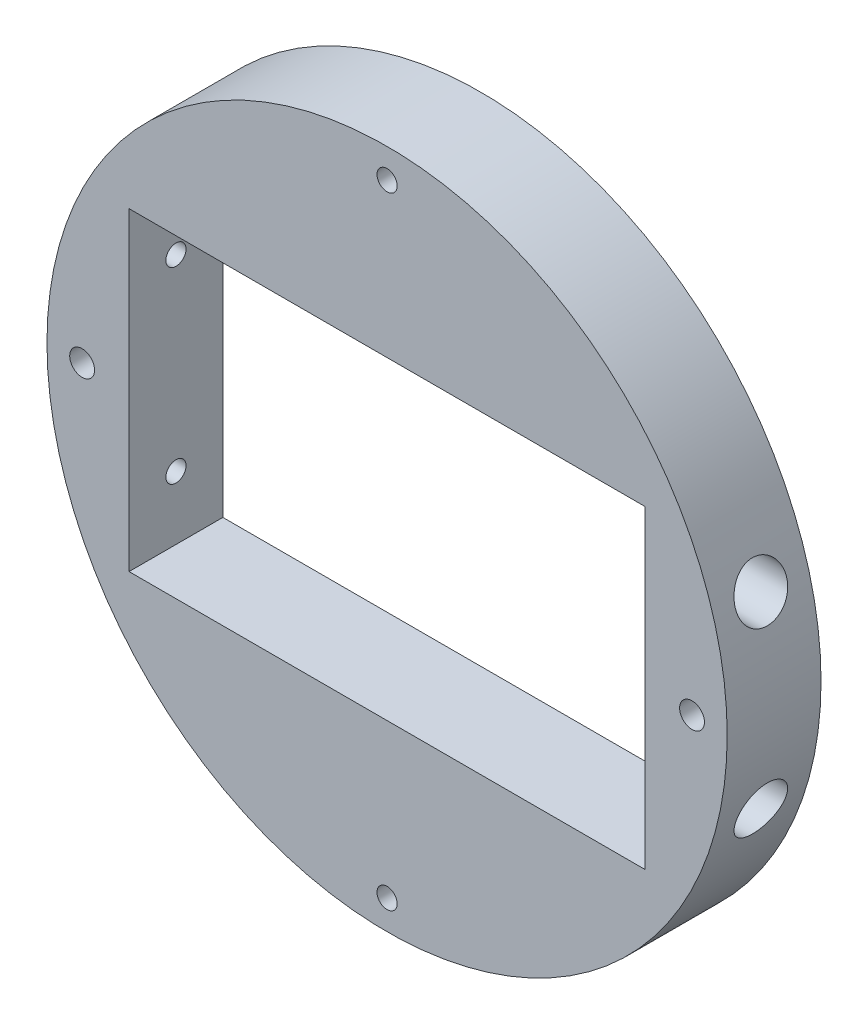
SolidWorks part; units mm, degrees
ref_plane "前视基准面" through (0, 0, 0) normal (0, 0, 1) x (1, 0, 0)
ref_plane "上视基准面" through (0, 0, 0) normal (0, 1, 0) x (1, 0, 0)
ref_plane "右视基准面" through (0, 0, 0) normal (1, 0, 0) x (0, 0, -1)
other "Configuration Table"
sketch "草图3" plane through (0, 0, 0) normal (0, 0, 1) x (1, 0, 0)
  line L1 (0, 72.5) -> (0, 60)
  line L2 (20, 60) -> (-20, 60) construction
  line L3 (0, -60) -> (0, -72.5)
  line L4 (-20, -60) -> (20, -60) construction
  line L5 (47, 33.5) -> (63, 33.5) construction
  line L6 (-55, -33.5) -> (55, -33.5)
  line L7 (-55, -33.5) -> (-55, 33.5)
  line L8 (-55, 33.5) -> (55, 33.5)
  line L9 (55, -33.5) -> (55, 33.5)
  line L10 (-55, -33.5) -> (55, 33.5) construction
  line L11 (-55, 33.5) -> (55, -33.5) construction
  circle A0 centre (0, 0) radius 72.5
  circle A1 centre (0, 66.25) radius 2.15
  circle A2 centre (0, -66.25) radius 2.15
  circle M2 centre (-55, -26.5) radius 3.6
  circle M3 centre (55, 26.5) radius 3.6
  circle M4 centre (65, 0) radius 2.65
  circle M13 centre (55, -26.5) radius 3.6
  circle M14 centre (-55, 26.5) radius 3.6
  circle M15 centre (-65, 0) radius 2.65
  line M16 (40, 40) -> (40, -40)
  arc M17 (40, -40) -> (20, -60) centre (20, -40) cw
  line M18 (20, -60) -> (-20, -60)
  arc M19 (-20, -60) -> (-40, -40) centre (-20, -40) cw
  line M20 (-40, -40) -> (-40, 40)
  arc M21 (-40, 40) -> (-20, 60) centre (-20, 40) cw
  line M22 (-20, 60) -> (20, 60)
  arc M23 (20, 60) -> (40, 40) centre (20, 40) cw
  dimension "D1" = 4.3
  dimension "D2" = 4.3
extrude "凸台-拉伸2" add sketch "草图3" along normal blind 20 contours A2 L3 L6 L7 L8 L1 A1 A0 M18 M19 M20 M2 M14 M21 M22 M15 | A2 L3 A0 L1 A1 L8 L9 L6 M22 M23 M16 M3 M13 M17 M18 M4 | L8 M20 M16 M23 M22 M21 | L6 M20 M19 M18 M17 M16 | L7 M14 | L7 M2 | L9 M3 | L9 M13 region at (50.1189, 50.1189, 0) region at (-1.6211, 70.45, 0) region at (0, 45.9761, 0) region at (0, -45.9761, 0) region at (-56.5279, 26.5, 0) region at (56.5279, 26.5, 0) region at (-56.5279, -26.5, 0) region at (56.5279, -26.5, 0)
sketch "草图5" plane through (-55, 0, 0) normal (1, 0, 0) x (0, 0, -1)
  line L0 (0, 0) -> (-20, 0)
  line L1 (-20, 72.5) -> (-20, -72.5) construction
  line L2 (-10, 0) -> (-10, 20)
  line L3 (-20, -33.5) -> (0, -33.5)
  line L4 (-20, -33.5) -> (-20, 33.5)
  line L5 (-20, 33.5) -> (0, 33.5)
  line L6 (0, -33.5) -> (0, 33.5)
  line L7 (-20, -33.5) -> (0, 33.5) construction
  line L8 (-20, 33.5) -> (0, -33.5) construction
  circle A0 centre (-10, 20) radius 2.15
  circle A1 centre (-10, -20) radius 2.15
  point P5 (-10, 0)
  dimension "D4" = 4.3
  dimension "D1" = 67
  dimension "D2" = 20
  dimension "D3" = 20
extrude "切除-拉伸2" cut sketch "草图5" against normal through all both and the other way through all contours A0 | A1 region at (-55, 21.4773, 11.4773) region at (-55, -20, 10)
ref_plane "基准面4" through (60, 0, 0) normal (1, 0, 0) x (0, 0, -1)
sketch "草图6" plane through (60, 0, 0) normal (1, 0, 0) x (0, 0, -1)
  circle A0 centre (-10, 20) radius 5.5
  circle A1 centre (-10, -20) radius 5.5
  dimension "D1" = 11
  dimension "D2" = 11
extrude "切除-拉伸4" cut sketch "草图6" along normal through all
mirror "镜向1" about plane through (0, 0, 0) normal (1, 0, 0) of "切除-拉伸4"
